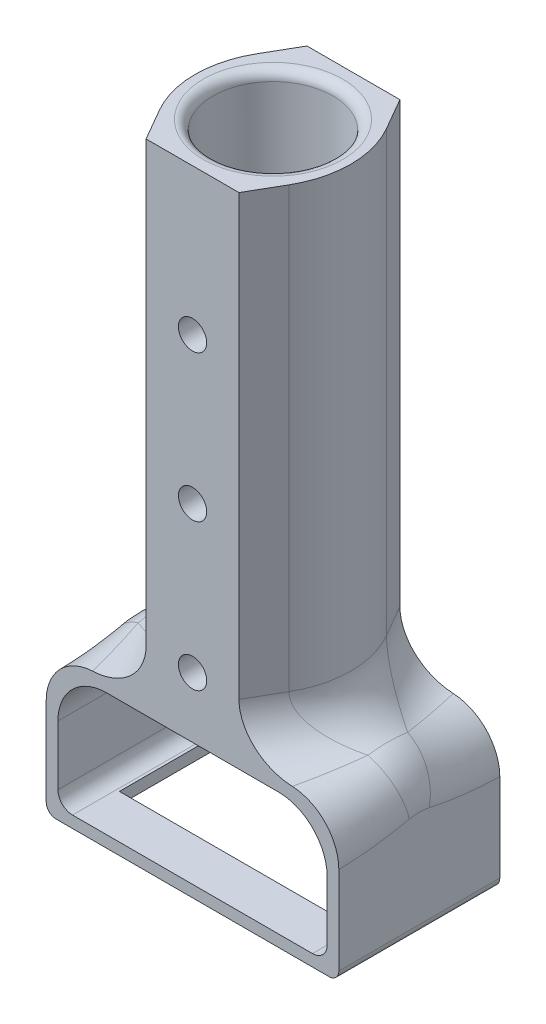
SolidWorks part; units mm, degrees
ref_plane "Front Plane" through (0, 0, 0) normal (0, 0, 1) x (1, 0, 0)
ref_plane "Top Plane" through (0, 0, 0) normal (0, 1, 0) x (1, 0, 0)
ref_plane "Right Plane" through (0, 0, 0) normal (1, 0, 0) x (0, 0, -1)
sketch "Sketch1" plane through (0, 0, 0) normal (0, 0, 1) x (1, 0, 0)
  line L0 (15, 22.832) -> (15, -11.1192) construction
  line L1 (0, 0) -> (30, 0)
  line L2 (0, 0) -> (0, 15)
  line L3 (0, 15) -> (30, 15)
  line L4 (30, 0) -> (30, 15)
  circle A0 centre (15, 4) radius 1
  point P9 (15, 0)
  point P10 (15, 15)
  dimension "D4" = 2
  dimension "D1" = 4
  dimension "D2" = 15
  dimension "D3" = 30
extrude "Boss-Extrude1" add sketch "Sketch1" along normal blind 2.5
sketch "Sketch2" plane through (0, 0, 2.5) normal (0, 0, 1) x (1, 0, 0)
  line L0 (1.2, 1.2) -> (1.2, 13.8)
  line L1 (0, 0) -> (30, 0)
  line L2 (0, 0) -> (0, 15)
  line L3 (0, 15) -> (30, 15)
  line L4 (30, 0) -> (30, 15)
  line L5 (1.2, 13.8) -> (28.8, 13.8)
  line L6 (28.8, 1.2) -> (28.8, 13.8)
  line L7 (1.2, 1.2) -> (28.8, 1.2)
  dimension "D1" = 1.2
extrude "Boss-Extrude2" add sketch "Sketch2" along normal blind 14
sketch "Sketch4" plane through (0, 15, 0) normal (0, 1, 0) x (1, 0, 0)
  line L0 (0, -8.25) -> (30, -8.25) construction
  line L1 (0, -16.5) -> (0, 0) construction
  line L2 (30, -16.5) -> (30, 0) construction
  line L3 (30, -8.25) -> (30, 0) construction
  line L4 (30, 0) -> (15, 0) construction
  line L5 (30, 0) -> (0, 0) construction
  line L6 (15, 0) -> (15, -16.5) construction
  line L7 (30, -16.5) -> (0, -16.5) construction
  circle A0 centre (15, -8.25) radius 6.15
  circle A1 centre (15, -8.25) radius 7.35
  dimension "D1" = 12.3
  dimension "D2" = 1.2
extrude "Boss-Extrude3" add sketch "Sketch4" along normal blind 50
sketch "Sketch5" plane through (0, 15, 0) normal (0, 1, 0) x (1, 0, 0)
  circle A0 centre (15, -8.25) radius 6.15 construction
  circle A1 centre (15, -8.25) radius 6.15
extrude "Cut-Extrude1" cut sketch "Sketch5" against normal up to surface (1.2 mm away) up to face at (15, 13.8, 9.5)
sketch "Sketch6" plane through (0, 15, 0) normal (0, 1, 0) x (1, 0, 0)
  line L0 (0, -8.25) -> (30, -8.25) construction
  line L1 (0, -16.5) -> (0, 0) construction
  line L2 (30, -16.5) -> (30, 0) construction
  line L3 (30, -8.25) -> (30, -16.5) construction
  line L4 (30, -16.5) -> (15, -16.5) construction
  line L5 (30, -16.5) -> (0, -16.5) construction
  line L6 (15, -16.5) -> (0, -16.5) construction
  line L7 (0, -16.5) -> (0, 0) construction
  line L8 (0, 0) -> (15, 0) construction
  line L9 (30, 0) -> (0, 0) construction
  line L10 (15, 0) -> (30, 0) construction
  line L12 (10.2369, -16.5) -> (19.7631, -16.5)
  line L13 (19.7631, -16.5) -> (24.5263, -8.25)
  line L14 (24.5263, -8.25) -> (19.7631, 0)
  line L15 (19.7631, 0) -> (10.2369, 0)
  line L16 (10.2369, 0) -> (5.4737, -8.25)
  line L17 (5.4737, -8.25) -> (10.2369, -16.5)
  circle A0 centre (15, -8.25) radius 8.25 construction
  circle A1 centre (15, -8.25) radius 6.15
  circle A2 centre (15, -8.25) radius 6.15 construction
extrude "Boss-Extrude4" add sketch "Sketch6" along normal up to surface (50 mm away) up to face at (15, 65, 15.6)
sketch "Sketch7" plane through (0, 0, 0) normal (0, -1, 0) x (-1, 0, 0)
  line L0 (-15, -16.5) -> (-15, 0) construction
  line L1 (0, -16.5) -> (-30, -16.5) construction
  line L2 (0, 0) -> (-30, 0) construction
  line L3 (-15, 0) -> (-15, -8.25) construction
  line L4 (-15, -8.25) -> (-30, -8.25) construction
  line L5 (-30, -16.5) -> (-30, 0) construction
  line L6 (-30, -8.25) -> (0, -8.25) construction
  line L7 (0, -16.5) -> (0, 0) construction
  line L9 (-3, -2) -> (-27, -2)
  line L10 (-3, -2) -> (-3, -12)
  line L11 (-3, -12) -> (-27, -12)
  line L12 (-27, -2) -> (-27, -12)
  line L13 (-3, -2) -> (-27, -12) construction
  line L14 (-3, -12) -> (-27, -2) construction
  point P13 (-15, -7)
  dimension "D1" = 10
  dimension "D2" = 1.25
  dimension "D3" = 3
  dimension "D4" = 3
extrude "Cut-Extrude2" cut sketch "Sketch7" against normal up to surface (1.2 mm away) up to face at (15, 1.2, 9.5)
sketch "Sketch9" plane through (0, 0, 16.5) normal (0, 0, 1) x (1, 0, 0)
  line L0 (15, 65) -> (15, 13.8) construction
  line L1 (10.2369, 65) -> (19.7631, 65) construction
  line L2 (28.8, 13.8) -> (1.2, 13.8) construction
  circle A0 centre (15, 50) radius 1.45
  circle A1 centre (15, 35) radius 1.45
  circle A2 centre (15, 20) radius 1.45
  dimension "D4" = 2.9
  dimension "D1" = 15
  dimension "D2" = 15
  dimension "D3" = 15
extrude "Cut-Extrude3" cut sketch "Sketch9" against normal up to next
fillet "Fillet1" radius 5 2 edges at (22.1447, 15, 4.125) (22.1447, 15, 12.375)
fillet "Fillet2" radius 5 2 edges at (7.8553, 15, 4.125) (7.8553, 15, 12.375)
fillet "Fillet3" radius 10 6 edges at (30, 15.0017, 8.5095) (26.1127, 16.5575, 8.25) (0, 15.0017, 7.9905) (3.8873, 16.5575, 8.25) (24.5263, 42.5, 8.25) (5.4737, 42.5, 8.25)
fillet "Fillet4" radius 5 2 edges at (28.8, 13.8, 9.5) (1.2, 13.8, 9.5)
fillet "Fillet5" radius 1.5 3 edges at (15, 13.8, 14.4) (28.8, 1.2, 9.5) (1.2, 1.2, 9.5)
fillet "Fillet6" radius 1 1 edges at (15, 65, 14.4)
fillet "Fillet7" radius 5 6 edges at (30, 15.0007, 7.9039) (30, 15.0007, 8.5961) (0, 15.0007, 8.5961) (0, 15.0007, 7.9039)
fillet "Fillet8" radius 1 2 edges at (30, 0, 8.25) (0, 0, 8.25)
sketch "Sketch10" plane through (0, 0, 16.5) normal (0, 0, 1) x (1, 0, 0)
  line L6 (1, 0) -> (29, 0)
  line L7 (30, 1) -> (30, 10.0108)
  line L8 (19.7631, 20) -> (19.7631, 65)
  line L9 (19.7631, 65) -> (10.2369, 65)
  line L10 (10.2369, 65) -> (10.2369, 20)
  line L11 (0, 10.0108) -> (0, 1)
  line L12 (1, 0) -> (29, 0)
  line L13 (30, 1) -> (30, 10.0108)
  line L14 (19.7631, 20) -> (19.7631, 65)
  line L15 (19.7631, 65) -> (10.2369, 65)
  line L16 (10.2369, 65) -> (10.2369, 20)
  line L17 (0, 10.0108) -> (0, 1)
  circle A1 centre (15, 4) radius 1
  arc A2 (29, 0) -> (30, 1) centre (29, 1) ccw
  arc A3 (0, 1) -> (1, 0) centre (1, 1) ccw
  arc A4 (29, 0) -> (30, 1) centre (29, 1) ccw
  arc A5 (0, 1) -> (1, 0) centre (1, 1) ccw
  circle A6 centre (15, 20) radius 1.45
  circle A7 centre (15, 35) radius 1.45
  ellipse E2 centre (25.5366, 20) end of major axis (19.7631, 20) minor radius 5 (19.7631, 20) -> (25.23, 15.0071) ccw
  ellipse E3 centre (4.4634, 20) end of major axis (10.2369, 20) minor radius 5 (4.77, 15.0071) -> (10.2369, 20) ccw
  ellipse E4 centre (25.5366, 20) end of major axis (19.7631, 20) minor radius 5 (19.7631, 20) -> (25.23, 15.0071) ccw
  ellipse E5 centre (4.4634, 20) end of major axis (10.2369, 20) minor radius 5 (4.77, 15.0071) -> (10.2369, 20) ccw
  spline S2 degree 3 poles (-3890.3441, -778.1229) (-421.8724, -146.9603) (37.4604, -28.2471) (29.8499, 11.2673) (29.7597, 11.5755) (29.5228, 12.1667) (29.3779, 12.4476) (29.0357, 12.9804) (28.8361, 13.2343) (28.3984, 13.6931) (28.1597, 13.9001) (27.642, 14.2689) (27.3629, 14.4299) (26.7876, 14.6924) (26.4887, 14.7962) (-5.366, 22.5216) (-105.2406, -278.1579) (3617.7343, -1710.475) knots -15.666501 -15.666501 -15.666501 -15.666501 0.125 0.125 0.25 0.25 0.375 0.375 0.5 0.5 0.625 0.625 0.75 0.75 0.875 0.875 13.568547 13.568547 13.568547 13.568547 only from (30, 10.0108) to (25.23, 15.0071)
  spline S3 degree 3 poles (972.4771, -3864.9696) (182.2814, -428.9622) (42.618, 24.2204) (3.5218, 14.7992) (3.2181, 14.6948) (2.6385, 14.4308) (2.3646, 14.273) (1.8482, 13.9064) (1.6039, 13.6952) (1.166, 13.2368) (0.9703, 12.9886) (0.6258, 12.4544) (0.478, 12.1681) (0.2424, 11.5813) (0.1526, 11.2779) (-6.1628, -21.2579) (305.5791, -107.8669) (1574.6836, 3670.4041) knots -15.656491 -15.656491 -15.656491 -15.656491 0.125 0.125 0.25 0.25 0.375 0.375 0.5 0.5 0.625 0.625 0.75 0.75 0.875 0.875 13.710199 13.710199 13.710199 13.710199 only from (4.77, 15.0071) to (0, 10.0108)
  spline S4 degree 3 poles (30, 10.0108) (30, 10.3313) (29.9695, 10.6466) (29.8499, 11.2673) (29.7597, 11.5755) (29.5228, 12.1667) (29.3779, 12.4476) (29.0357, 12.9804) (28.8361, 13.2343) (28.3984, 13.6931) (28.1597, 13.9001) (27.642, 14.2689) (27.3629, 14.4299) (26.7876, 14.6924) (26.4887, 14.7962) (25.8674, 14.9469) (25.5502, 14.9923) (25.23, 15.0071) knots 0 0 0 0 0.125 0.125 0.25 0.25 0.375 0.375 0.5 0.5 0.625 0.625 0.75 0.75 0.875 0.875 1 1 1 1
  spline S5 degree 3 poles (4.77, 15.0071) (4.4498, 14.9923) (4.1363, 14.9473) (3.5218, 14.7992) (3.2181, 14.6948) (2.6385, 14.4308) (2.3646, 14.273) (1.8482, 13.9064) (1.6039, 13.6952) (1.166, 13.2368) (0.9703, 12.9886) (0.6258, 12.4544) (0.478, 12.1681) (0.2424, 11.5813) (0.1526, 11.2779) (0.0308, 10.6503) (0, 10.3313) (0, 10.0108) knots 0 0 0 0 0.125 0.125 0.25 0.25 0.375 0.375 0.5 0.5 0.625 0.625 0.75 0.75 0.875 0.875 1 1 1 1
  dimension "D1" = 0
